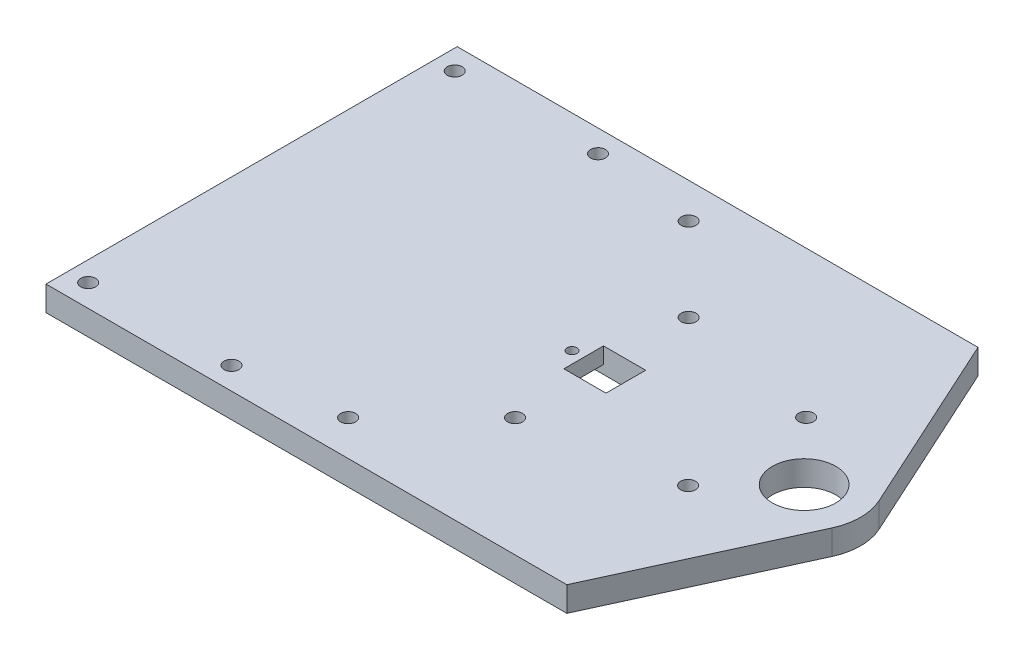
SolidWorks part; units mm, degrees
ref_plane "Front Plane" through (0, 0, 0) normal (0, 0, 1) x (1, 0, 0)
ref_plane "Top Plane" through (0, 0, 0) normal (0, 1, 0) x (1, 0, 0)
ref_plane "Right Plane" through (0, 0, 0) normal (1, 0, 0) x (0, 0, -1)
sketch "Sketch1" plane through (0, 0, 0) normal (0, 1, 0) x (1, 0, 0)
  line L0 (-32.5, 41.5) -> (-32.5, -41.4) construction
  line L1 (-67.5, 41.5) -> (37.5, 41.5)
  line L2 (-67.5, 41.5) -> (-67.5, -41.4)
  line L3 (-67.5, -41.4) -> (37.5, -41.4)
  line L4 (37.5, 41.5) -> (37.5, -41.4)
  line L5 (0, 0) -> (63.1136, 0) construction
  line L6 (37.5, 41.5) -> (54.3074, 4.7404)
  line L7 (37.5, -41.4) -> (54.3025, -4.7511)
  circle A0 centre (43.9397, 0) radius 6.4
  circle A1 centre (43.9397, 0) radius 11.4
  point P0 (0, 0)
  point P14 (44.0318, 0)
  point P16 (43.9397, 0)
  dimension "D5" = 12.8
  dimension "D6" = 5
  dimension "D1" = 35
  dimension "D2" = 82.9
  dimension "D3" = 70
  dimension "D4" = 41.5
extrude "Boss-Extrude1" add sketch "Sketch1" along normal blind 5 contours A1 L4 L1 L2 L3 | L4 A1 | A1 L6 L4 | A1 L4 A0 | A1 L4 L7 region at (-15.383, 0, -0.0504) region at (42.3792, 0, -20.7537) region at (46.9121, 0, -10.7055) region at (35.4735, 0, 0) region at (42.3764, 0, 20.7214)
sketch "Sketch7" plane through (0, 0, 0) normal (0, -1, 0) x (1, 0, 0)
  circle A0 centre (-34.6, 36.9) radius 1.5
  circle A1 centre (-63.5, 36.9) radius 1.5
  circle A2 centre (-63.5, -37) radius 1.5
  circle A3 centre (-34.6, -37) radius 1.5
extrude "Cut-Extrude4" cut sketch "Sketch7" against normal blind 10
sketch "Sketch9" plane through (0, 0, 0) normal (0, -1, 0) x (1, 0, 0)
  line L0 (-65.5, 26.505) -> (-65.5, -23.995)
  line L1 (-62.5, 23.505) -> (-38.7, 23.505)
  line L2 (-62.5, 23.505) -> (-62.5, -20.995)
  line L3 (-62.5, -20.995) -> (-38.7, -20.995)
  line L4 (-38.7, 23.505) -> (-38.7, -20.995)
  line L5 (-65.5, -23.995) -> (-35.7, -23.995)
  line L6 (-35.7, 26.505) -> (-35.7, -23.995)
  line L7 (-65.5, 26.505) -> (-35.7, 26.505)
  line L8 (-62.5, 26.505) -> (-62.5, -23.995)
  line L9 (-62.5, -20.995) -> (-64.5, -18.995)
  line L10 (-64.5, -18.995) -> (-64.5, -23.995)
  line L11 (-64.5, -23.995) -> (-62.5, -23.995)
  line L12 (-62.5, 23.505) -> (-64.5, 21.505)
  line L13 (-64.5, 21.505) -> (-64.5, 26.505)
  line L14 (-64.5, 26.505) -> (-62.5, 26.505)
  dimension "D2" = 2
  dimension "D3" = 2
  dimension "D4" = 45
  dimension "D1" = 3
extrude "Boss-Extrude2" add sketch "Sketch9" along normal blind 10 contours L7 L8 L1 L4 L3 L5 L6 region at (-49.1, 0, 25.9333)
extrude "Boss-Extrude3" add sketch "Sketch9<3>" along normal blind 4 contours L13 L12 L8 L7 | L9 L10 L5 L8 region at (-63.5833, 0, 24.4633) region at (-63.5833, 0, -21.9533)
sketch "Sketch9<3>" plane through (0, 0, 0) normal (0, -1, 0) x (1, 0, 0) same geometry as "Sketch9"
fillet "Fillet1" radius 2 2 edges at (-62.5, -4, 25.005) (-62.5, -4, -22.495)
fillet "Fillet2" radius 2 2 edges at (-35.7, -5, 26.505) (-35.7, -5, -23.995)
sketch "Sketch12" plane through (0, 0, 0) normal (0, -1, 0) x (1, 0, 0)
  circle A0 centre (32.4, 11.85) radius 1.5
  circle A1 centre (32.4, -11.95) radius 1.5
  circle A2 centre (3.1159, -17.5468) radius 1.5
  circle A3 centre (-13.7132, -34.3759) radius 1.5
  circle A4 centre (3.1159, 17.4468) radius 1.5
  circle A5 centre (-13.7132, 34.2759) radius 1.5
  dimension "D1" = 3
  dimension "D2" = 3
  dimension "D3" = 3
  dimension "D4" = 3
  dimension "D5" = 3
  dimension "D6" = 3
extrude "Cut-Extrude5" cut sketch "Sketch12" against normal blind 13
sketch "Sketch13" plane through (0, 0, 0) normal (0, -1, 0) x (1, 0, 0)
  line L0 (-0.5, 4) -> (-0.5, -4)
  line L1 (-5, 4) -> (8, 4)
  line L2 (-5, 4) -> (-5, -4)
  line L3 (-5, -4) -> (8, -4)
  line L4 (8, 4) -> (8, -4)
  line L5 (-5, 4) -> (8, -4) construction
  line L6 (-5, -4) -> (8, 4) construction
  line L7 (15.5, -10.05) -> (15.5, 14.95) construction
  circle A0 centre (-3.85, 0) radius 3
  point P0 (1.5, 0)
  point P12 (-1.35, 0)
  dimension "D6" = 6
  dimension "D7" = 1.15
  dimension "D1" = 13
  dimension "D2" = 8
  dimension "D3" = 4.5
  dimension "D4" = 4
  dimension "D5" = 7.5
extrude "Cut-Extrude6" cut sketch "Sketch13" against normal blind 13 contours L4 L1 L0 L3 region at (3.75, 0, 0)
extrude "Cut-Extrude7" cut sketch "Sketch13<3>" against normal blind 1.75 contours L2 L3 L0 L1 | L2 A0 | L2 A0 region at (-0.5918, 0, 0) region at (-3.1703, 0, 0) region at (-5.7639, 0, 0)
sketch "Sketch13<3>" plane through (0, 0, 0) normal (0, -1, 0) x (1, 0, 0) same geometry as "Sketch13"
sketch "Sketch15" plane through (0, 1.75, 0) normal (0, -1, 0) x (1, 0, 0)
  line L0 (-5, 4) -> (-5, 2.7708) construction
  circle A0 centre (-2.85, 0) radius 1
  dimension "D1" = 2
  dimension "D2" = 2.15
extrude "Cut-Extrude9" cut sketch "Sketch15" against normal blind 10
